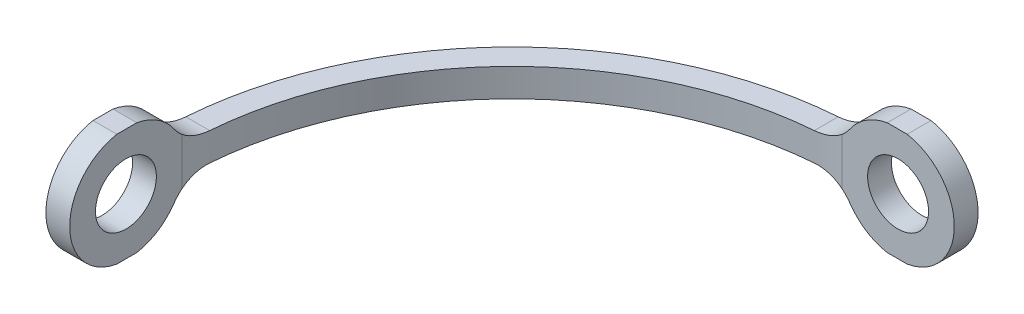
SolidWorks part; units mm, degrees
ref_plane "Front Plane" through (0, 0, 0) normal (0, 0, 1) x (1, 0, 0)
ref_plane "Top Plane" through (0, 0, 0) normal (0, 1, 0) x (1, 0, 0)
ref_plane "Right Plane" through (0, 0, 0) normal (1, 0, 0) x (0, 0, -1)
sketch "Sketch1" plane through (0, 0, 0) normal (0, 1, 0) x (1, 0, 0)
  line L0 (-26.5437, 0) -> (0, 0) construction
  line L1 (-3.75, 25.75) -> (3.75, 25.75)
  line L2 (-3.75, 25.75) -> (-3.75, 27.3375)
  line L3 (-3.75, 27.3375) -> (3.75, 27.3375)
  line L4 (3.75, 25.75) -> (3.75, 27.3375)
  line L5 (-3.75, 25.75) -> (3.75, 27.3375) construction
  line L6 (-3.75, 27.3375) -> (3.75, 25.75) construction
  line L7 (-27.3375, 3.75) -> (-25.75, 3.75)
  line L8 (-27.3375, 3.75) -> (-27.3375, -3.75)
  line L9 (-27.3375, -3.75) -> (-25.75, -3.75)
  line L10 (-25.75, 3.75) -> (-25.75, -3.75)
  line L11 (-27.3375, 3.75) -> (-25.75, -3.75) construction
  line L12 (-27.3375, -3.75) -> (-25.75, 3.75) construction
  line L13 (0, 0) -> (0, 26.5437) construction
  arc A0 (-25.75, 3.75) -> (-3.75, 25.75) centre (-3.75, 3.75) cw
  arc A1 (-27.3375, 3.75) -> (-3.75, 27.3375) centre (-3.75, 3.75) cw
  point P0 (0, 26.5437)
  point P5 (-26.5437, 0)
  dimension "D3" = 22
  dimension "D1" = 1.5875
  dimension "D2" = 7.5
extrude "Boss-Extrude1" add sketch "Sketch1" along normal mid plane 7.5 contours L10 L7 L8 L9 | L1 L4 L3 L2 region at (0, 0, -26.5437) region at (-26.5437, 0, 0)
extrude "Boss-Extrude2" add sketch "Sketch1<3>" along normal mid plane 1.875 contours A1 L7 A0 L2 region at (-19.5422, 0, -19.5422)
sketch "Sketch1<3>" plane through (0, 0, 0) normal (0, 1, 0) x (1, 0, 0) same geometry as "Sketch1"
sketch "Sketch2" plane through (0, 0, -25.75) normal (0, 0, 1) x (1, 0, 0)
  line L0 (3.75, 3.75) -> (3.75, -3.75) construction
  circle A0 centre (0, 0) radius 2.032
  circle A2 centre (-0.0586, 0) radius 3.8086
  point P4 (3.75, 0)
  line M3 (3.75, -3.75) -> (3.75, 3.75)
  line M6 (-3.75, -3.75) -> (3.75, -3.75)
  line M7 (3.75, 3.75) -> (-3.75, 3.75)
  line M8 (-3.75, 3.75) -> (-3.75, 0.9375)
  line M10 (-3.75, -0.9375) -> (-3.75, -3.75)
  dimension "D1" = 4.064
extrude "Cut-Extrude1" cut sketch "Sketch2" against normal through all contours A0 | M7 M8 | M3 M7 | M6 M3 | M10 M6 region at (0, 0, -25.75) region at (-2.967, 3.0059, -25.75) region at (-2.967, -3.0059, -25.75) region at (2.9557, 2.9023, -25.75) region at (2.9557, -2.9023, -25.75)
sketch "Sketch3" plane through (-25.75, 0, 0) normal (1, 0, 0) x (0, 0, -1)
  circle A0 centre (0, 0) radius 2.032
  circle A1 centre (0.0586, 0) radius 3.8086
  line M1 (-3.75, -3.75) -> (3.75, -3.75)
  line M2 (3.75, -3.75) -> (3.75, -0.9375)
  line M4 (3.75, 0.9375) -> (3.75, 3.75)
  line M5 (3.75, 3.75) -> (-3.75, 3.75)
  line M6 (-3.75, 3.75) -> (-3.75, -3.75)
  dimension "D1" = 4.064
extrude "Cut-Extrude2" cut sketch "Sketch3" against normal through all contours A0 | A1 M6 M1 | A1 M5 M6 | A1 M4 M5 | A1 M1 M2 region at (-25.75, 0, 0) region at (-25.75, 3.0059, -2.967) region at (-25.75, -3.0059, -2.967) region at (-25.75, 2.9023, 2.9557) region at (-25.75, -2.9023, 2.9557)
fillet "Fillet5" radius 2.8125 4 edges at (-3.75, -0.9375, -26.5437) (-3.75, 0.9375, -26.5437) (-26.5437, -0.9375, -3.75) (-26.5437, 0.9375, -3.75)
